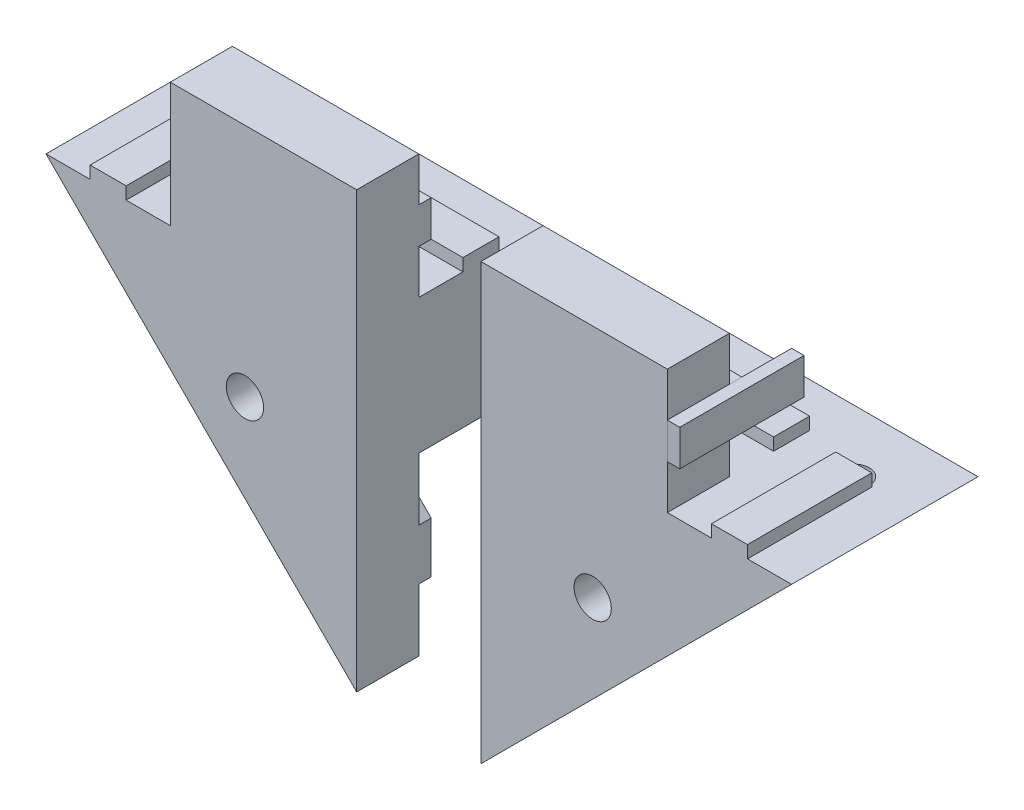
SolidWorks part; units mm, degrees
ref_plane "Front Plane" through (0, 0, 0) normal (0, 0, 1) x (1, 0, 0)
ref_plane "Top Plane" through (0, 0, 0) normal (0, 1, 0) x (1, 0, 0)
ref_plane "Right Plane" through (0, 0, 0) normal (1, 0, 0) x (0, 0, -1)
ref_plane "FrontPlane+10mm" through (0, 0, 10) normal (0, 0, 1) x (1, 0, 0)
sketch "Sketch1" plane through (0, 0, 0) normal (0, 0, 1) x (1, 0, 0)
  line L0 (-290, 0) -> (-10, 0) construction
  line L1 (0, 0) -> (-90, -90) construction
  line L2 (-10, 0) -> (0, 0) construction
  line L3 (-10, 0) -> (-10, 10) construction
  line L4 (-10, 10) -> (0, 10) construction
  line L5 (0, 0) -> (0, 10) construction
  line L6 (-90, -90) -> (-210, -90) construction
  line L7 (-300, 10) -> (-290, 10) construction
  line L8 (-300, 10) -> (-300, 0) construction
  line L9 (0, 0) -> (-10, 0)
  line L10 (-290, 10) -> (-290, 0) construction
  line L11 (-210, -90) -> (-300, 0) construction
  line L12 (-88.1335, -73.9914) -> (-16.0086, -1.8665) construction
  line L13 (-100, -80) -> (-90, -80) construction
  line L14 (-100, -80) -> (-100, -90) construction
  line L15 (-10, 0) -> (-10, 10)
  line L16 (-90, -80) -> (-90, -90) construction
  line L17 (-16.0086, -1.8665) -> (-8.9376, -8.9376) construction
  line L18 (-88.1335, -73.9914) -> (-81.0624, -81.0624) construction
  line L19 (-16.0086, -1.8665) -> (0, 0) construction
  line L20 (-88.1335, -73.9914) -> (-90, -90) construction
  line L21 (-10, 10) -> (-25, 10)
  line L22 (0, 0) -> (-8.9376, -8.9376)
  line L23 (-8.9376, -8.9376) -> (-16.0086, -1.8665)
  line L24 (-16.0086, -1.8665) -> (-25, -10.8579)
  line L25 (-25, -10.8579) -> (-25, 10)
  dimension "D1" = 10
  dimension "D2" = 10
  dimension "D3" = 300
  dimension "D4" = 10
  dimension "D5" = 120
  dimension "D6" = 135
  dimension "D7" = 45
  dimension "D8" = 45
  dimension "D9" = 127.2792
  dimension "D10" = 10
  dimension "D11" = 10
  dimension "D12" = 10
  dimension "D13" = 102
  dimension "D14" = 25
extrude "Main" add sketch "Sketch1" along normal blind 15
sketch "Sketch4" plane through (0, 0, 0) normal (0, 0, -1) x (-1, 0, 0)
  line L1 (10, 0) -> (25, 0)
  line L2 (10, 0) -> (10, 10)
  line L3 (10, 10) -> (25, 10)
  line L4 (25, 0) -> (25, 10)
extrude "Cut-Extrude2" cut sketch "Sketch4" against normal blind 10
sketch "Sketch2" plane through (0, 0, 10) normal (0, 0, -1) x (-1, 0, 0)
  line L0 (10, 0) -> (10, 10) construction
  line L1 (10, 6.45) -> (25, 6.45)
  line L2 (10, 6.45) -> (10, 3.55)
  line L3 (10, 3.55) -> (25, 3.55)
  line L4 (25, 6.45) -> (25, 3.55)
  line L5 (25, 0) -> (25, -10.8579) construction
  line L6 (10, 10) -> (25, 10) construction
  dimension "D1" = 3.55
  dimension "D2" = 2.9
extrude "Boss-Extrude3" add sketch "Sketch2" along normal blind 1
sketch "Sketch5" plane through (-7.0711, 7.0711, 0) normal (0.7071, -0.7071, 0) x (0, 0, -1)
  line L0 (-15, -25.3553) -> (0, -25.3553) construction
  line L1 (-3.55, -25.3553) -> (-6.45, -25.3553)
  line L2 (-3.55, -25.3553) -> (-3.55, -12.6396)
  line L3 (-3.55, -12.6396) -> (-6.45, -12.6396)
  line L4 (-6.45, -25.3553) -> (-6.45, -12.6396)
  line L5 (-15, -12.6396) -> (0, -12.6396) construction
  line L6 (0, -25.3553) -> (0, -12.6396) construction
  dimension "D1" = 3.55
  dimension "D2" = 2.9
extrude "Boss-Extrude4" add sketch "Sketch5" along normal blind 1
sketch "Sketch6" plane through (0, 0, 10) normal (0, 0, 1) x (1, 0, 0)
  line L0 (-25, -10.8579) -> (-16.0086, -1.8665)
  line L1 (-16.0086, -1.8665) -> (-8.9376, -8.9376)
  line L2 (-8.9376, -8.9376) -> (-25, -25)
  line L3 (-25, -10.8579) -> (-25, -25)
  line L4 (-12.4731, -5.402) -> (-19.5442, -12.4731) construction
  circle A0 centre (-16.0086, -8.9376) radius 1.5
  point P13 (-16.0086, -8.9376)
  dimension "D1" = 3
  dimension "D2" = 22.7157
  dimension "D3" = 14.1421
  dimension "D4" = 5
extrude "Boss-Extrude5" add sketch "Sketch6" along normal blind 5
sketch "Sketch7" plane through (0, 0, 10) normal (0, 0, -1) x (-1, 0, 0)
  line L0 (13.4984, -4.3767) -> (25, -15.8783)
  line L1 (25, -10.8579) -> (25, -25) construction
  line L3 (25, -15.8783) -> (25, -19.9795)
  line L4 (25, -19.9795) -> (11.4478, -6.4273)
  line L5 (11.4478, -6.4273) -> (13.4984, -4.3767)
  line L7 (8.9376, -8.9376) -> (16.0086, -1.8665) construction
  line L8 (16.0086, -1.8665) -> (8.9376, -8.9376) construction
  line L10 (25, -25) -> (0, 0) construction
  point P8 (15.2239, -13.4218)
  dimension "D1" = 2.9
  dimension "D2" = 3.55
extrude "Boss-Extrude6" add sketch "Sketch7" along normal blind 1
sketch "Sketch8" plane through (0, 0, 0) normal (0, 1, 0) x (1, 0, 0)
  line L0 (0, -15) -> (-10, -15) construction
  line L1 (-3.55, -15) -> (-6.45, -15)
  line L2 (-3.55, -15) -> (-3.55, -5)
  line L3 (-3.55, -5) -> (-6.45, -5)
  line L4 (-6.45, -15) -> (-6.45, -5)
  line L5 (0, -15) -> (0, 0) construction
  dimension "D1" = 3.55
  dimension "D2" = 2.9
  dimension "D3" = 10
extrude "Boss-Extrude7" add sketch "Sketch8" along normal blind 1
sketch "Sketch9" plane through (0, 0, 15) normal (0, 0, 1) x (1, 0, 0)
  line L0 (-10, 0) -> (-10, 10) construction
  line L1 (-10, 6.45) -> (-9, 6.45)
  line L2 (-10, 6.45) -> (-10, 3.55)
  line L3 (-10, 3.55) -> (-9, 3.55)
  line L4 (-9, 6.45) -> (-9, 3.55)
  line L5 (-10, 10) -> (-25, 10) construction
  dimension "D1" = 1
  dimension "D2" = 3.55
  dimension "D3" = 2.9
extrude "Boss-Extrude8" add sketch "Sketch9" against normal blind 10 separate body
sketch "Sketch11" plane through (0, 0, 0) normal (0, 1, 0) x (1, 0, 0)
  line L0 (0, -15) -> (0, 0) construction
  line L1 (0, 0) -> (-25, 0) construction
  circle A0 centre (-5, -5) radius 1.25
  dimension "D1" = 2.5
  dimension "D2" = 5
  dimension "D3" = 5
extrude "Cut-Extrude4" cut sketch "Sketch11" against normal through all
sketch "Sketch12" plane through (0, 0, 15) normal (0, 0, 1) x (1, 0, 0)
  circle A0 centre (-16.0086, -8.9376) radius 1.5
  arc A1 (-14.7117, -9.6913) -> (-16.7624, -7.6407) centre (-16.0086, -8.9376) ccw construction
extrude "Cut-Extrude5" cut sketch "Sketch12" against normal through all
sketch "Sketch13" plane through (0, 0, 0) normal (0, 1, 0) x (1, 0, 0)
  line L0 (-25, -10) -> (-25, 0) construction
  line L1 (-10, -3.55) -> (-25, -3.55)
  line L2 (-10, -3.55) -> (-10, -6.45)
  line L3 (-10, -6.45) -> (-25, -6.45)
  line L4 (-25, -3.55) -> (-25, -6.45)
  line L5 (0, -15) -> (0, 0) construction
  line L6 (0, 0) -> (-25, 0) construction
  dimension "D1" = 10
  dimension "D2" = 2.9
  dimension "D3" = 3.55
extrude "Boss-Extrude9" add sketch "Sketch13" along normal blind 1
ref_plane "Plane1" through (-30, 0, 0) normal (-1, 0, 0) x (0, 0, 1)
mirror "Mirror1" about plane through (-30, 0, 0) normal (-1, 0, 0) of bodies 115
